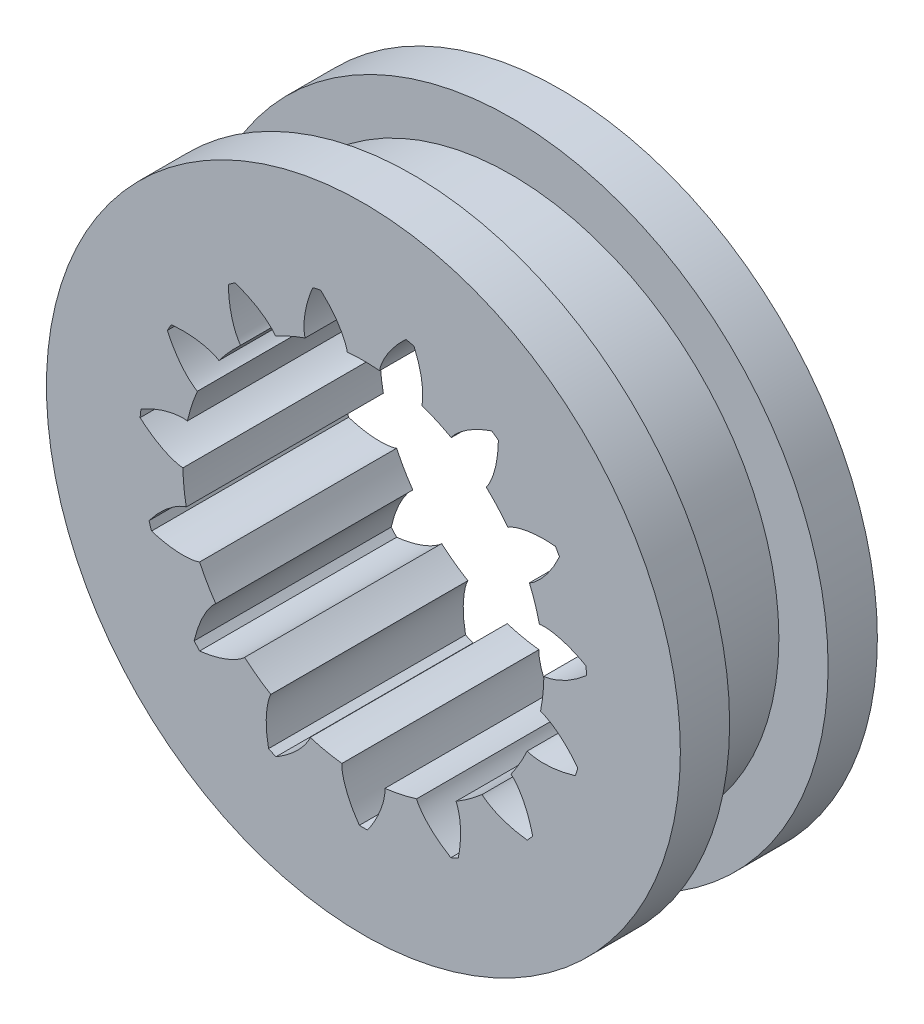
SolidWorks part; units mm, degrees
ref_plane "前视基准面" through (0, 0, 0) normal (0, 0, 1) x (1, 0, 0)
ref_plane "上视基准面" through (0, 0, 0) normal (0, 1, 0) x (1, 0, 0)
ref_plane "右视基准面" through (0, 0, 0) normal (1, 0, 0) x (0, 0, -1)
sketch "草图1" plane through (0, 0, 0) normal (0, 0, 1) x (1, 0, 0)
  circle A0 centre (0, 0) radius 4.55
  circle A1 centre (0, 0) radius 5.4352
extrude "凸台-拉伸1" add sketch "草图1" along normal blind 4
ref_axis "基准轴1" through (0, 0, 4) along (0, 0, -1)
sketch "草图2" plane through (0, 0, 0) normal (0, 0, 1) x (1, 0, 0)
  line L0 (0, 0) -> (0, 3.6648) construction
  arc A0 (0.3287, 3.65) -> (-0.3287, 3.65) centre (0, 0) ccw
  arc A1 (1.0502, 4.6236) -> (-1.0502, 4.6236) centre (0, 0) ccw
  spline S0 degree 3 poles (0.3287, 3.65) (0.3302, 3.6621) (0.3333, 3.6776) (0.3381, 3.697) (0.3413, 3.7091) (0.3452, 3.7225) (0.3498, 3.7373) (0.3551, 3.7533) (0.3613, 3.7707) (0.3683, 3.7892) (0.3762, 3.809) (0.3851, 3.83) (0.395, 3.8521) (0.406, 3.8754) (0.4181, 3.8998) (0.4313, 3.9252) (0.4458, 3.9516) (0.4615, 3.979) (0.4785, 4.0073) (0.4969, 4.0365) (0.5166, 4.0666) (0.5378, 4.0975) (0.5604, 4.1291) (0.5846, 4.1615) (0.6103, 4.1945) (0.6375, 4.2282) (0.6664, 4.2624) (0.6969, 4.2971) (0.7291, 4.3324) (0.763, 4.368) (0.7987, 4.4039) (0.8361, 4.4402) (0.8753, 4.4767) (0.9163, 4.5134) (0.9742, 4.5632) (1.0193, 4.5996) (1.0502, 4.6236) knots 0 0 0 0 0.029439 0.038395 0.048538 0.059868 0.072386 0.086091 0.100983 0.117063 0.13433 0.152784 0.172425 0.193254 0.21527 0.238473 0.262863 0.288441 0.315206 0.343158 0.372298 0.402625 0.434139 0.46684 0.500729 0.535805 0.572068 0.609518 0.648156 0.687981 0.728993 0.771193 0.81458 0.859154 0.904915 1 1 1 1
  spline S1 degree 3 poles (-0.3287, 3.65) (-0.3302, 3.6621) (-0.3333, 3.6776) (-0.3381, 3.697) (-0.3413, 3.7091) (-0.3452, 3.7225) (-0.3498, 3.7373) (-0.3551, 3.7533) (-0.3613, 3.7707) (-0.3683, 3.7892) (-0.3762, 3.809) (-0.3851, 3.83) (-0.395, 3.8521) (-0.406, 3.8754) (-0.4181, 3.8998) (-0.4313, 3.9252) (-0.4458, 3.9516) (-0.4615, 3.979) (-0.4785, 4.0073) (-0.4969, 4.0365) (-0.5166, 4.0666) (-0.5378, 4.0975) (-0.5604, 4.1291) (-0.5846, 4.1615) (-0.6103, 4.1945) (-0.6375, 4.2282) (-0.6664, 4.2624) (-0.6969, 4.2971) (-0.7291, 4.3324) (-0.763, 4.368) (-0.7987, 4.4039) (-0.8361, 4.4402) (-0.8753, 4.4767) (-0.9163, 4.5134) (-0.9742, 4.5632) (-1.0193, 4.5996) (-1.0502, 4.6236) knots 0 0 0 0 0.029439 0.038395 0.048538 0.059868 0.072386 0.086091 0.100983 0.117063 0.13433 0.152784 0.172425 0.193254 0.21527 0.238473 0.262863 0.288441 0.315206 0.343158 0.372298 0.402625 0.434139 0.46684 0.500729 0.535805 0.572068 0.609518 0.648156 0.687981 0.728993 0.771193 0.81458 0.859154 0.904915 1 1 1 1
extrude "凸台-拉伸2" add sketch "草图2" along normal blind 4
pattern_circular "阵列(圆周)1" count 15 every 24 about axis through (0, 0, 4) along (0, 0, -1) of "凸台-拉伸2"
sketch "草图3" plane through (0, 0, 0) normal (0, 0, 1) x (1, 0, 0)
  circle A0 centre (0, 0) radius 3.9 construction
  dimension "Dn" = 7.8
sketch "草图5" plane through (0, 0, 4) normal (0, 0, 1) x (1, 0, 0)
  circle A0 centre (0, 0) radius 6.4352
  circle A1 centre (0, 0) radius 5.4352 construction
  circle A2 centre (0, 0) radius 5.4352
  dimension "D1" = 1
extrude "凸台-拉伸3" add sketch "草图5" against normal blind 1
extrude "凸台-拉伸4" add sketch "草图5<2>" along normal blind 1 from surface starting at face at (0, 0, 0)
sketch "草图5<2>" plane through (0, 0, 4) normal (0, 0, 1) x (1, 0, 0) same geometry as "草图5"
